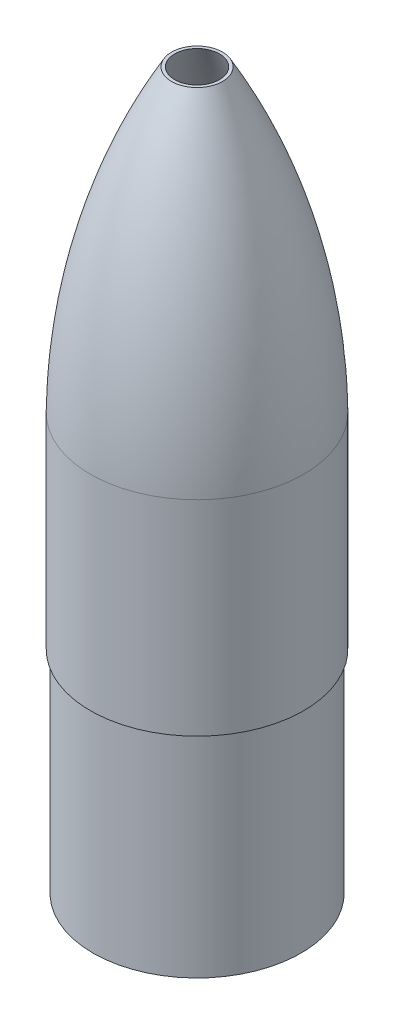
SolidWorks part; units mm, degrees
material "A-Glass Fiber"
ref_plane "Front Plane" through (0, 0, 0) normal (0, 0, 1) x (1, 0, 0)
ref_plane "Top Plane" through (0, 0, 0) normal (0, 1, 0) x (1, 0, 0)
ref_plane "Right Plane" through (0, 0, 0) normal (1, 0, 0) x (0, 0, -1)
sketch "Sketch1" plane through (0, 0, 0) normal (0, 0, 1) x (1, 0, 0)
  line L0 (78.16, 0.5558) -> (78.16, 150.5558)
  line L3 (0, 0) -> (0, 614.1078) construction
  line L6 (0, -198.8179) -> (0, -350.074)
  line L7 (76.2, 0.5558) -> (76.2, 150.5443)
  line L8 (78.16, 0.5558) -> (76.2, 0.5558)
  line L9 (0, 400) -> (0, 396.4892)
  spline S0 degree 4 poles (-15.3468, 421.2955) (-15.0103, 420.856) (-14.3388, 419.9758) (-13.3353, 418.6515) (-12.0074, 416.8814) (-10.6914, 415.1091) (-9.395, 413.3458) (-8.1033, 411.5702) (-6.8448, 409.8242) (-5.5578, 408.0177) (-4.3521, 406.3128) (-3.0104, 404.3884) (-1.9663, 402.8848) (-0.427, 400.6308) (0.2737, 399.5978) (1.5381, 397.7184) (2.5222, 396.2406) (3.5056, 394.7509) (4.501, 393.2308) (5.4828, 391.7179) (6.46, 390.199) (7.4365, 388.6679) (8.4121, 387.1246) (16.4914, 374.2288) (28.348, 353.3444) (42.5411, 323.7528) (57.5292, 282.9984) (68.4498, 242.8729) (74.1096, 210.0768) (76.6559, 184.8086) (77.5185, 170.0675) (77.6804, 166.8514) (77.8002, 164.1053) (77.872, 162.2907) (77.9363, 160.4857) (77.9934, 158.6832) (78.0434, 156.8667) (78.0859, 155.0826) (78.1211, 153.3065) (78.1553, 151.0401) (78.1694, 149.7893) (78.1915, 147.0488) (78.1921, 145.2128) (78.1883, 142.8552) (78.1709, 140.7595) (78.1445, 138.5315) (78.1069, 136.371) (78.059, 134.1662) (78, 131.9694) (77.93, 129.7536) (77.8488, 127.533) (77.7798, 125.8658) (77.7301, 124.7552) (77.7044, 124.2) knots 0 0 0 0 0 0.006969 0.013937 0.020906 0.027875 0.034717 0.04156 0.048403 0.055246 0.062088 0.068931 0.075774 0.082616 0.0883 0.093983 0.099666 0.10535 0.111033 0.116716 0.122399 0.128083 0.133891 0.1397 0.313954 0.430124 0.546294 0.685698 0.836718 0.848335 0.865761 0.871569 0.877253 0.882936 0.888619 0.894302 0.899986 0.905669 0.911352 0.917035 0.923907 0.930779 0.93765 0.944522 0.951393 0.958265 0.965136 0.972008 0.979006 0.986004 0.993002 1 1 1 1 1 construction
  spline S1 degree 4 poles (0, 400) (0.2113, 399.6881) (0.6358, 399.0596) (1.5381, 397.7184) (2.5222, 396.2406) (3.5056, 394.7509) (4.501, 393.2308) (5.4828, 391.7179) (6.46, 390.199) (7.4365, 388.6679) (8.4121, 387.1246) (16.4914, 374.2288) (28.348, 353.3444) (42.5411, 323.7528) (57.5292, 282.9984) (68.4498, 242.8729) (74.1096, 210.0768) (76.6559, 184.8086) (77.5185, 170.0675) (77.6804, 166.8514) (77.8002, 164.1053) (77.872, 162.2907) (77.9363, 160.4857) (77.9934, 158.6832) (78.0434, 156.8667) (78.0859, 155.0826) (78.1211, 153.3065) (78.1455, 151.6911) (78.1556, 150.9325) (78.16, 150.5558) knots 0.082616 0.082616 0.082616 0.082616 0.082616 0.0883 0.093983 0.099666 0.10535 0.111033 0.116716 0.122399 0.128083 0.133891 0.1397 0.313954 0.430124 0.546294 0.685698 0.836718 0.848335 0.865761 0.871569 0.877253 0.882936 0.888619 0.894302 0.899986 0.905669 0.911352 0.917035 0.917035 0.917035 0.917035 0.917035
  spline S2 degree 1 poles (-1.6226, 398.9005) (76.2, 150.5443) knots 0 0 1 1 construction
  spline S3 degree 3 poles (-1.6226, 398.9005) (-1.4527, 398.6498) (-1.1386, 398.1849) (-0.5196, 397.2651) (0.1099, 396.3257) (0.6873, 395.459) (1.2483, 394.6123) (1.9995, 393.4729) (3.323, 391.4513) (5.1827, 388.5671) (9.5921, 381.5907) (18.7945, 366.2671) (36.7943, 332.2032) (57.0765, 280.9241) (69.6847, 227.2404) (74.343, 188.9958) (75.531, 171.161) (75.8913, 162.9157) (76.0101, 159.4861) (76.0769, 157.0706) (76.1102, 155.7062) (76.1328, 154.6907) (76.1533, 153.65) (76.1724, 152.5206) (76.189, 151.4097) (76.1964, 150.8476) (76.2, 150.5443) knots 0.082616 0.082616 0.082616 0.082616 0.085876 0.089135 0.092394 0.095654 0.098913 0.102172 0.108691 0.121728 0.134765 0.186913 0.29121 0.499804 0.708398 0.812695 0.864843 0.877881 0.890918 0.897436 0.900696 0.903955 0.907214 0.910473 0.913733 0.916992 0.916992 0.916992 0.916992 only from (0, 396.4892) to (76.2, 150.5443)
  point P11 (0, 400)
  dimension "D1" = 400
  dimension "D2" = 150
  dimension "D3" = 1.96
  dimension "D4" = 76.2
revolve "Revolve3" add sketch "Sketch1" angle 360 about L6 reverse direction yes
ref_plane "Plane1" through (0, 150.5558, 0) normal (0, 1, 0) x (1, 0, 0)
sketch "Sketch2" plane through (0, 150.5558, 0) normal (0, 1, 0) x (1, 0, 0)
  circle A0 centre (0, 0) radius 76.2 construction
  circle A1 centre (0, 0) radius 76.2
  circle A2 centre (0, 0) radius 73.2
  dimension "D1" = 3
extrude "Boss-Extrude1" add sketch "Sketch2" against normal blind 304.8
ref_plane "Plane2" through (0, 400, 0) normal (0, -1, 0) x (-1, 0, 0)
sketch "Sketch3" plane through (0, 400, 0) normal (0, -1, 0) x (-1, 0, 0)
  circle A0 centre (0, 0) radius 126.4604
extrude "Cut-Extrude1" cut sketch "Sketch3" along normal blind 30 contours A0
